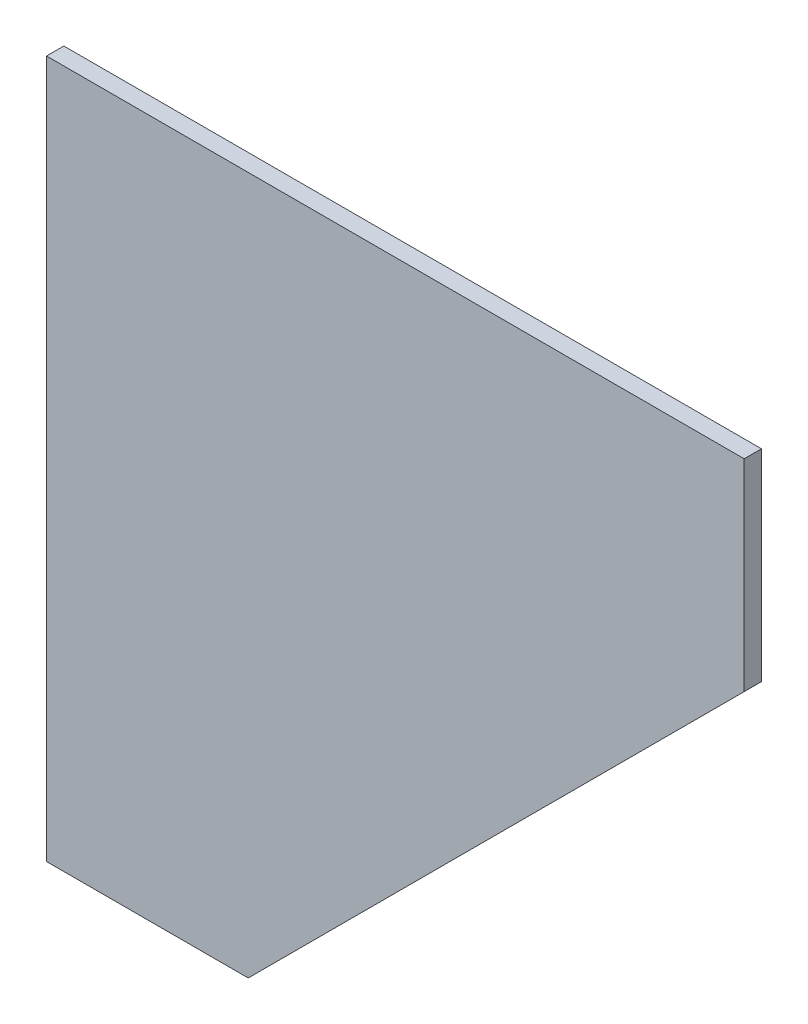
SolidWorks part; units mm, degrees
material "AISI 1020"
ref_plane "Спереди" through (0, 0, 0) normal (0, 0, 1) x (1, 0, 0)
ref_plane "Сверху" through (0, 0, 0) normal (0, 1, 0) x (1, 0, 0)
ref_plane "Справа" through (0, 0, 0) normal (1, 0, 0) x (0, 0, -1)
sketch "Эскиз1" plane through (0, 0, 0) normal (0, 0, 1) x (1, 0, 0)
  line L0 (292.132, -50) -> (50, -50)
  line L2 (50, -50) -> (50, -292.132)
  line L4 (50, -292.132) -> (120, -292.132)
  line L5 (120, -292.132) -> (292.132, -120)
  line L6 (292.132, -120) -> (292.132, -50)
  line L7 (4234.322, -100) -> (100, -100) construction
  line L10 (100, 2500) -> (100, -2560) construction
  dimension "D1" = 50
  dimension "D2" = 50
  dimension "D3" = 20
  dimension "D4" = 20
  dimension "D5" = 150
base flange "Базовая кромка1" sketch "Эскиз1" thickness 6 reverse thickness direction no parameters "D1"=0.75
sketch "Сгиб-Линии1" plane through (0, 0, 0) normal (0, 1, 0) x (1, 0, 0)
sketch "Граничная рамка1" plane through (0, 0, 0) normal (0, 1, 0) x (1, 0, 0)
sheet metal parameters "Листовой металл3" thickness 6 parameters "D1"=0.75
flat pattern "Развертка3" [suppressed]
sketch "Сгиб-Линии2" plane through (0, 0, 0) normal (0, 1, 0) x (1, 0, 0)
sketch "Граничная рамка2" [suppressed] plane through (0, 0, 0) normal (0, 1, 0) x (1, 0, 0)
